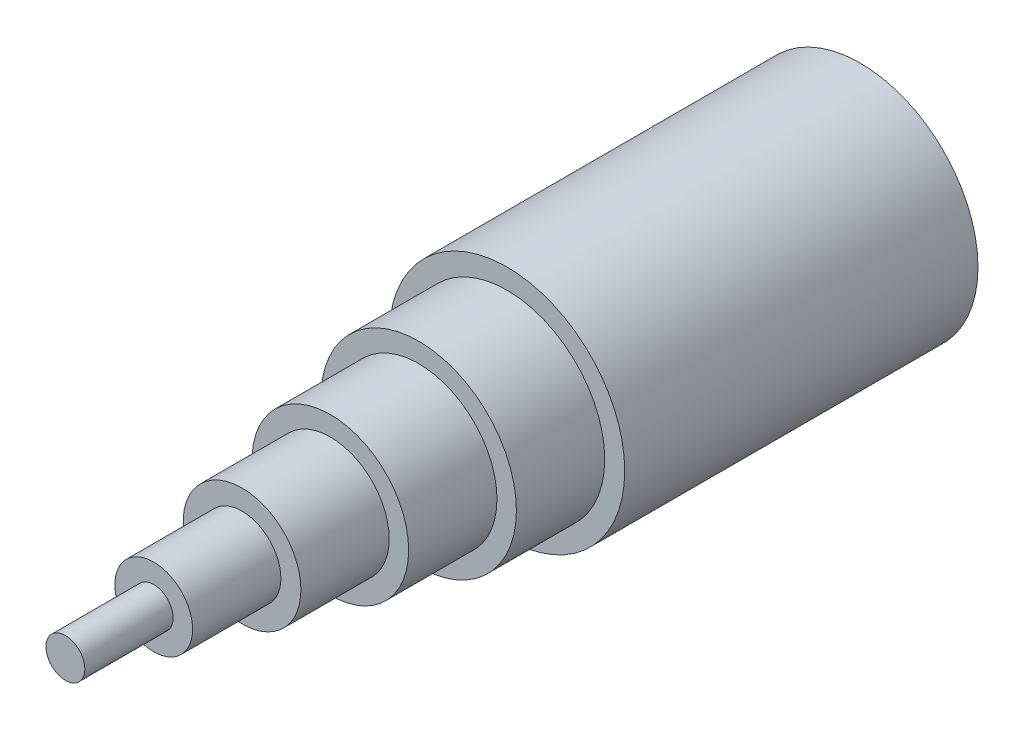
SolidWorks part; units mm, degrees
ref_plane "Front Plane" through (0, 0, 0) normal (0, 0, 1) x (1, 0, 0)
ref_plane "Top Plane" through (0, 0, 0) normal (0, 1, 0) x (1, 0, 0)
ref_plane "Right Plane" through (0, 0, 0) normal (1, 0, 0) x (0, 0, -1)
sketch "Sketch1" plane through (0, 0, 0) normal (0, 0, 1) x (1, 0, 0)
  circle A0 centre (0, 0) radius 1
  dimension "D1" = 2
extrude "Boss-Extrude1" add sketch "Sketch1" along normal blind 3
sketch "Sketch2" plane through (0, 0, 3) normal (0, 0, 1) x (1, 0, 0)
  circle A0 centre (0, 0) radius 0.83
  circle A1 centre (0, 0) radius 0.33
  circle A2 centre (0, 0) radius 0.5
  circle A3 centre (0, 0) radius 0.665
  circle A4 centre (0, 0) radius 0.165
  dimension "D1" = 1.66
  dimension "D2" = 0.66
  dimension "D3" = 1
  dimension "D4" = 1.33
  dimension "D5" = 0.33
extrude "Boss-Extrude2" add sketch "Sketch2" along normal blind 3 contours A1 region at (-0.3207, 0, 3)
extrude "Boss-Extrude3" add sketch "Sketch2<3>" along normal blind 2.25 contours A2 A1 region at (-0.4859, 0, 3)
sketch "Sketch2<3>" plane through (0, 0, 3) normal (0, 0, 1) x (1, 0, 0) same geometry as "Sketch2"
extrude "Boss-Extrude4" add sketch "Sketch2<4>" along normal blind 1.5 contours A3 A2 region at (-0.6462, 0, 3)
sketch "Sketch2<4>" plane through (0, 0, 3) normal (0, 0, 1) x (1, 0, 0) same geometry as "Sketch2"
extrude "Boss-Extrude6" add sketch "Sketch2<6>" along normal blind 0.75 contours A0 A3 region at (-0.8065, 0, 3)
sketch "Sketch2<6>" plane through (0, 0, 3) normal (0, 0, 1) x (1, 0, 0) same geometry as "Sketch2"
extrude "Boss-Extrude7" add sketch "Sketch2<7>" along normal blind 3.75 contours A4 region at (0, 0, 3)
sketch "Sketch2<7>" plane through (0, 0, 3) normal (0, 0, 1) x (1, 0, 0) same geometry as "Sketch2"
